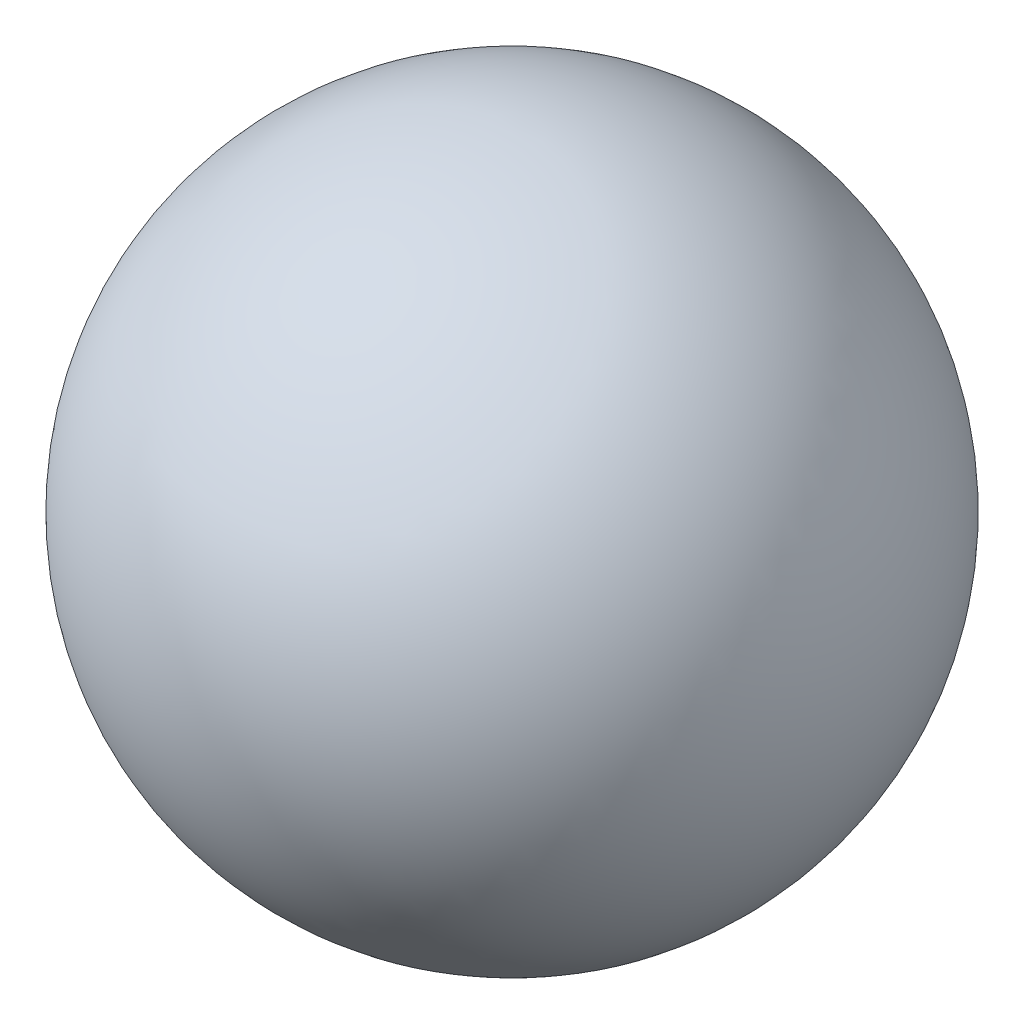
SolidWorks part; units mm, degrees
material "ｼﾘｺﾝ ｺﾞﾑ"
ref_plane "正面" through (0, 0, 0) normal (0, 0, 1) x (1, 0, 0)
ref_plane "平面" through (0, 0, 0) normal (0, 1, 0) x (1, 0, 0)
ref_plane "右側面" through (0, 0, 0) normal (1, 0, 0) x (0, 0, -1)
sketch "ｽｹｯﾁ1" plane through (0, 0, 0) normal (0, 0, 1) x (1, 0, 0)
  line L0 (0, -126.5) -> (0, 126.5) construction
  line L1 (0, 125) -> (0, -125)
  arc A0 (0, 125) -> (0, -125) centre (0, 0) cw
  dimension "D1" = 250
revolve "回転1" add sketch "ｽｹｯﾁ1" angle 360 about L1 region at (53.0516, 0, 0)
